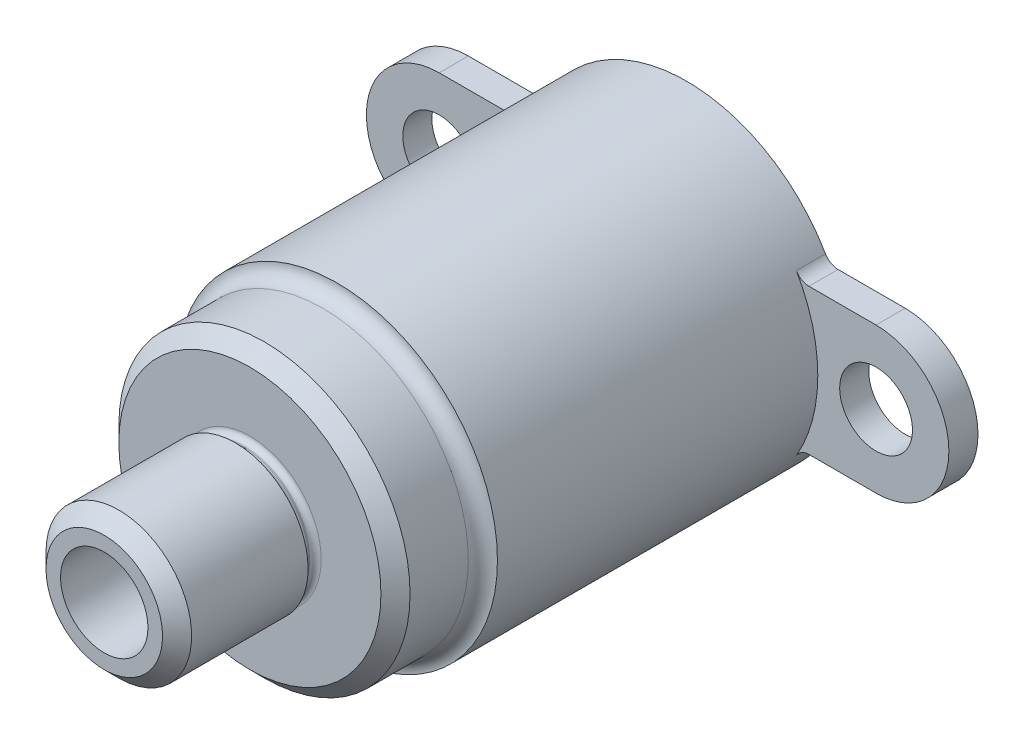
SolidWorks part; units mm, degrees
ref_plane "Спереди" through (0, 0, 0) normal (0, 0, 1) x (1, 0, 0)
ref_plane "Сверху" through (0, 0, 0) normal (0, 1, 0) x (1, 0, 0)
ref_plane "Справа" through (0, 0, 0) normal (1, 0, 0) x (0, 0, -1)
sketch "Эскиз1" plane through (0, 0, 0) normal (1, 0, 0) x (0, 0, -1)
  line L0 (-28.643, 0) -> (42.3762, 0) construction
  line L1 (30, 11) -> (0, 11)
  line L2 (30, 10) -> (25, 10)
  line L3 (30, 11) -> (30, 10)
  line L4 (2, 8) -> (25, 8)
  line L5 (25, 8) -> (25, 10)
  line L6 (-10, 5) -> (0, 5)
  line L7 (-10, 3) -> (2, 3)
  line L8 (0, 11) -> (0, 5)
  line L9 (2, 8) -> (2, 3)
  line L10 (-10, 3) -> (-10, 5)
  dimension "D1" = 30
  dimension "D2" = 22
  dimension "D3" = 20
  dimension "D4" = 2
  dimension "D5" = 5
  dimension "D6" = 10
  dimension "D7" = 6
  dimension "D8" = 10
  dimension "D9" = 2
revolve "Повернуть1" add sketch "Эскиз1" angle 360 about L0
cosmetic thread "Условное изображение резьбы1" parameters "D2"=18.344
sketch "Эскиз2" plane through (0, 0, 0) normal (0, 1, 0) x (1, 0, 0)
  line L0 (4.5, 0) -> (5, 0)
  line L1 (5, 0) -> (5, -1)
  line L2 (5, -10) -> (5, 0) construction
  line L4 (4.5, -0.7) -> (4.5, 0)
  line L5 (0, 0) -> (0, -7.3244) construction
  line L6 (5, -1) -> (4.5, -0.7)
  dimension "D1" = 0.5
  dimension "D2" = 1
  dimension "D3" = 0.7
revolve "Вырез-Повернуть1" cut sketch "Эскиз2" angle 360 about L5
fillet "Скругление1" radius 0.4 2 edges at (-4.5, 0, 0) (-4.5, 0, 0.7)
sketch "Эскиз3" plane through (0, 0, 0) normal (0, 1, 0) x (1, 0, 0)
  line L0 (0, 0) -> (0, 36.5873) construction
  line L1 (-10, 25) -> (-10.2236, 25)
  line L2 (-10.2236, 25) -> (-10.2236, 25.5)
  line L4 (-10, 25.7) -> (-10, 25)
  line L7 (-10.2236, 25.5) -> (-10, 25.7)
  line L8 (-10, 30) -> (-10, 25) construction
  dimension "D1" = 0.3
  dimension "D2" = 0.5
  dimension "D3" = 0.7
revolve "Вырез-Повернуть2" cut sketch "Эскиз3" angle 360 about L0
fillet "Скругление2" radius 0.2 2 edges at (10.2236, 0, -25.5) (10.2236, 0, -25)
fillet "Скругление3" radius 1 1 edges at (8, 0, -2)
sketch "Эскиз4" plane through (0, 0, -30) normal (0, 0, -1) x (-1, 0, 0)
  line L0 (-22.9294, 0) -> (20.459, 0) construction
  line L1 (-15, 5) -> (-9.798, 5)
  line L2 (-15, -5) -> (-9.798, -5)
  arc A0 (-9.798, 5) -> (-9.798, -5) centre (0, 0) ccw
  circle A1 centre (0, 0) radius 11 construction
  arc A2 (-15, 5) -> (-15, -5) centre (-15, 0) ccw
  dimension "D1" = 15
  dimension "D2" = 5
extrude "Бобышка-Вытянуть1" add sketch "Эскиз4" against normal blind 2
hole_wizard "Диаметр отверстия Ø5.0 (5)1" positions "Эскиз5" profile "Эскиз6" hole size "Ø5.0" standard "Ansi Metric" end condition through all
sketch "Эскиз5" plane through (0, 0, -30) normal (0, 0, -1) x (-1, 0, 0)
  point P0 (-15, 0)
sketch "Эскиз6" plane through (15, 0, -30) normal (1, 0, 0) x (0, 1, 0)
  line L0 (0, 0) -> (0, 40)
  line L1 (0, 40) -> (2.5, 40)
  line L2 (2.5, 40) -> (2.5, 0)
  line L5 (2.5, 0) -> (0, 0)
  line L11 (0, -6.35) -> (0, 107.95) construction
  dimension "Диаметр сквозного отверстия" = 5
  dimension "Глубина сквозного отверстия" = 40
mirror "Зеркальное отражение1" about plane through (0, 0, 0) normal (1, 0, 0) of "Бобышка-Вытянуть1", "Диаметр отверстия Ø5.0 (5)1"
chamfer "Фаска2" distance 0.5 angle 45 1 edges at (10, 0, -30)
fillet "Скругление4" radius 1 4 edges at (-9.798, -5, -29) (-9.798, 5, -29) (9.798, -5, -29) (9.798, 5, -29)
chamfer "Фаска1" distance 1 angle 45 2 edges at (5, 0, 10) (8, 0, -25)
sketch "Эскиз7" plane through (0, 0, 0) normal (1, 0, 0) x (0, 0, -1)
  line L0 (0, 11) -> (6, 11)
  line L1 (6, 11) -> (6, 10)
  line L2 (6, 10) -> (0, 10)
  line L3 (0, 10) -> (0, 11)
  line L4 (0, 0) -> (18.304, 0) construction
  dimension "D1" = 6
  dimension "D2" = 20
revolve "Вырез-Повернуть3" cut sketch "Эскиз7" angle 360 about L4
fillet "Скругление5" radius 1 1 edges at (10, 0, -6)
chamfer "Фаска3" distance 1 angle 45 1 edges at (10, 0, 0)
